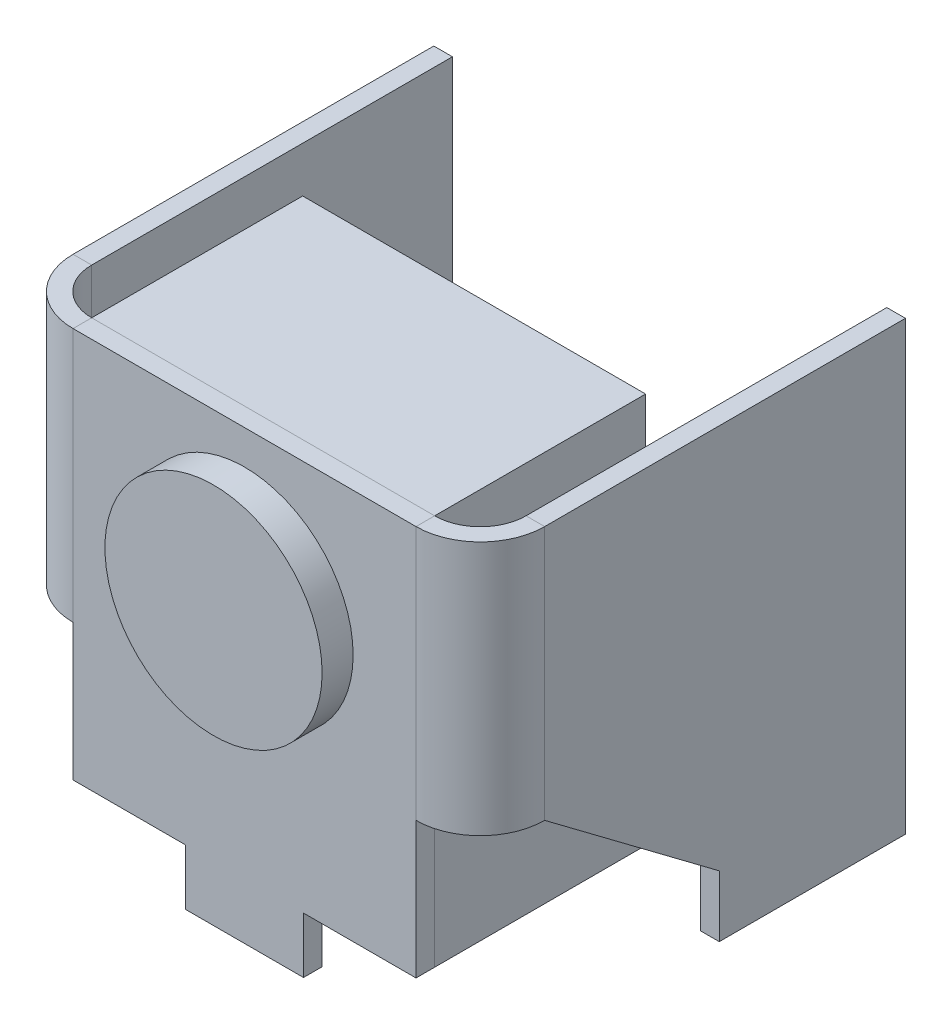
SolidWorks part; units mm, degrees
note: The reader was unsure of these and kept them because the rebuilt part matched: flange length of "Edge-Flange2".
ref_plane "Front Plane" through (0, 0, 0) normal (0, 0, 1) x (1, 0, 0)
ref_plane "Top Plane" through (0, 0, 0) normal (0, 1, 0) x (1, 0, 0)
ref_plane "Right Plane" through (0, 0, 0) normal (1, 0, 0) x (0, 0, -1)
sketch "Sketch4" plane through (0, 0, 0) normal (0, 0, 1) x (1, 0, 0)
  line L1 (0, -3.6) -> (-3.8, -3.6)
  line L2 (0, -3.6) -> (0, 3.6)
  line L3 (0, 3.6) -> (-3.8, 3.6)
  line L4 (-3.8, -3.6) -> (-3.8, 3.6)
  line L5 (0, -3.6) -> (-3.8, 3.6) construction
  line L6 (0, 3.6) -> (-3.8, -3.6) construction
  point P0 (-1.9, 0)
  point P6 (0, 0)
  dimension "D1" = 7.2
  dimension "D2" = 3.8
sheet metal parameters "Sheet-Metal1" thickness 0.3 parameters "D1"=0.7366
base flange "Base-Flange1" sketch "Sketch4" thickness 0.3 reverse thickness direction no parameters "D1"=0.7366
edge flange "Edge-Flange2" sketch "Sketch12" flange angle 90 flange length 6.55 flange position material inside bend radius 0.7366 thickness 0.3 relief rectangular parameters "D6"=10
sketch "Sketch12" plane through (-3.8, 0, -0.3) normal (-1, 0, 0) x (0, 1, 0)
  line L0 (3.6, 0) -> (-3.6, 0) construction
  line L1 (3.6, 0) -> (-3.6, 0)
  line L2 (-3.6, 0) -> (-3.6, 6.55)
  line L3 (-3.6, 6.55) -> (3.6, 6.55)
  line L4 (3.6, 6.55) -> (3.6, 0)
bend "EdgeBend2" bend radius 0.7366 bend angle 90 parameters "D5"=2
sketch "Sketch13" plane through (0, 0, 0) normal (0, 0, 1) x (1, 0, 0)
  line L0 (0, -3.6) -> (0, 3.6) construction
  line L1 (-2.7634, -3.6) -> (-0.95, -3.6)
  line L2 (-2.7634, -3.6) -> (-2.7634, -2.7)
  line L3 (-2.7634, -2.7) -> (-0.95, -2.7)
  line L4 (-0.95, -3.6) -> (-0.95, -2.7)
  dimension "D1" = 0.9
  dimension "D2" = 0.95
extrude "Cut-Extrude1" cut sketch "Sketch13" against normal blind 0.3 normal cut yes
sketch "Sketch14" plane through (-3.8, 0, 0) normal (-1, 0, 0) x (0, 0, 1)
  line L0 (0, -0.5) -> (0, -3.6)
  line L1 (0, 3.6) -> (-1.0366, 3.6) construction
  line L2 (-3.85, -2.6113) -> (-1.0366, -0.5)
  line L3 (-1.0366, 3.6) -> (-1.0366, -3.6) construction
  line L4 (-1.0366, -0.5) -> (0, -0.5)
  line L5 (0, -3.6) -> (-3.85, -3.6)
  line L12 (-6.85, -3.6) -> (-1.0366, -3.6) construction
  line L13 (-3.85, -3.6) -> (-3.85, -2.6113)
  line L14 (-6.85, 3.6) -> (-6.85, -3.6) construction
  dimension "D1" = 3
  dimension "D2" = 4.1
extrude "Cut-Extrude3" cut sketch "Sketch14" against normal up to vertex (1.0366 mm away) normal cut yes up to point (-2.7634, -2.7, 0)
mirror "Mirror3" about plane through (0, -3.6, -0.3) normal (1, 0, 0) of bodies 110
bend "MirrorBend2" bend radius 0.7366 bend angle 90 parameters "D5"=3
sketch "Sketch17" plane through (0, 0, -0.3) normal (0, 0, -1) x (-1, 0, 0)
  line L1 (-2.7634, -2.7) -> (2.7634, -2.7)
  line L2 (-2.7634, -2.7) -> (-2.7634, 3.6)
  line L3 (-2.7634, 3.6) -> (2.7634, 3.6)
  line L4 (2.7634, -2.7) -> (2.7634, 3.6)
extrude "Boss-Extrude3" add sketch "Sketch17" along normal blind 3.4 separate body
sketch "Sketch18" plane through (0, 0, -0.3) normal (0, 0, 1) x (1, 0, 0)
  line L0 (-2.7634, 1.3) -> (2.7634, 1.3) construction
  line L3 (2.7634, -2.7) -> (-2.7634, -2.7) construction
  circle A0 centre (0, 1.3) radius 1.75
  dimension "D1" = 4
extrude "Boss-Extrude4" add sketch "Sketch18" along normal blind 0.8
flat pattern "Flat-Pattern1" [suppressed]
sketch "Bend-Lines1" [suppressed] plane through (0, 0, 0) normal (0, 1, 0) x (1, 0, 0)
sketch3d "Bounding-Box1" [suppressed]
  line L0 (3.8, -3.6, 0) -> (-3.8, -3.6, 0) construction
  line L1 (3.8, 3.6, 0) -> (-3.8, 3.6, 0) construction
  line L2 (3.8, -3.6, 0) -> (3.8, 3.6, 0) construction
  line L3 (-3.8, -3.6, 0) -> (-3.8, 3.6, 0) construction
bend of the flat pattern "Flatten-<EdgeBend2>1" [suppressed]
bend of the flat pattern "Flatten-<MirrorBend2>1" [suppressed]
